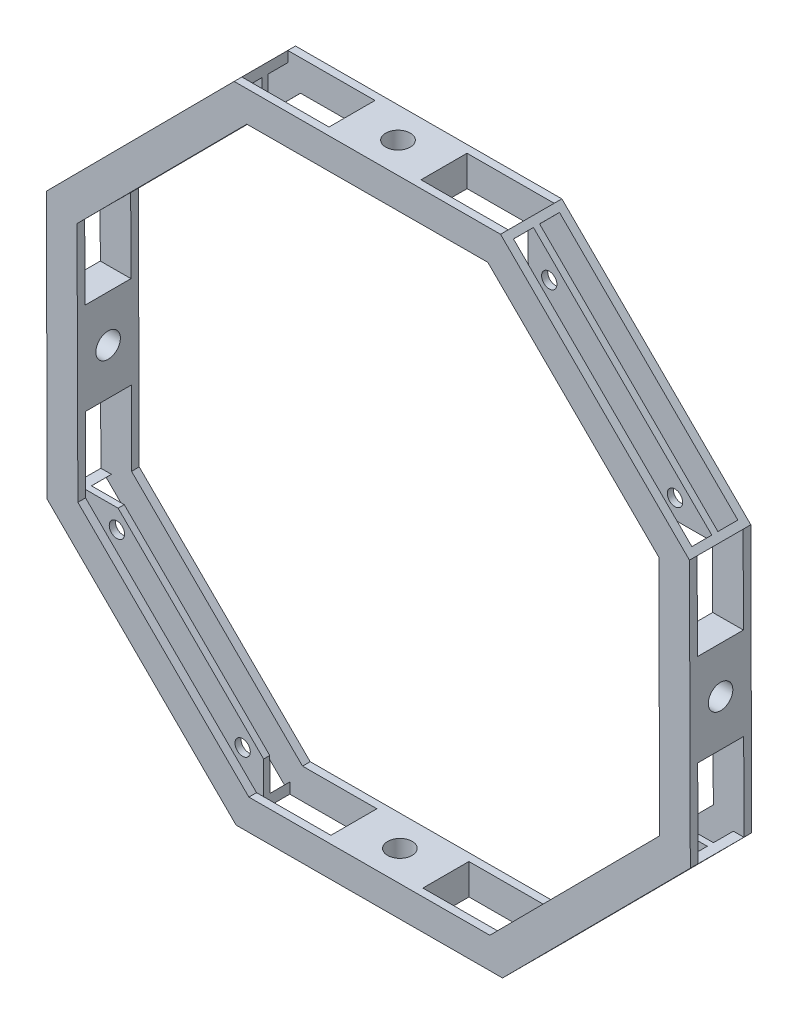
SolidWorks part; units mm, degrees
ref_plane "Plano frontal" through (0, 0, 0) normal (0, 0, 1) x (1, 0, 0)
ref_plane "Plano superior" through (0, 0, 0) normal (0, 1, 0) x (1, 0, 0)
ref_plane "Plano direito" through (0, 0, 0) normal (1, 0, 0) x (0, 0, -1)
sketch "Esboço1" plane through (0, 0, 0) normal (0, 0, 1) x (1, 0, 0)
  line L9 (209.462, 87.5228) -> (86.2241, 210)
  line L10 (86.2241, 210) -> (-87.5228, 209.462)
  line L11 (-87.5228, 209.462) -> (-210, 86.2241)
  line L12 (-210, 86.2241) -> (-209.462, -87.5228)
  line L13 (-209.462, -87.5228) -> (-86.2241, -210)
  line L14 (-86.2241, -210) -> (87.5228, -209.462)
  line L15 (87.5228, -209.462) -> (210, -86.2241)
  line L16 (210, -86.2241) -> (209.462, 87.5228)
  line L17 (189.4504, 79.2502) -> (77.9233, 190)
  line L18 (77.9233, 190) -> (-79.2502, 189.4504)
  line L19 (-79.2502, 189.4504) -> (-190, 77.9233)
  line L20 (-190, 77.9233) -> (-189.4504, -79.2502)
  line L21 (-189.4504, -79.2502) -> (-77.9233, -190)
  line L22 (-77.9233, -190) -> (79.2502, -189.4504)
  line L23 (79.2502, -189.4504) -> (190, -77.9233)
  line L24 (190, -77.9233) -> (189.4504, 79.2502)
  circle A0 centre (0, 0) radius 209.732 construction
  circle A1 centre (0, 0) radius 189.7264 construction
extrude "Ressalto-extrusão1" add sketch "Esboço1" along normal blind 40
sketch "Esboço2" plane through (209.731, 0.6494, 0) normal (1, 0.0031, 0) x (0, 0, -1)
  line L0 (-40, 86.8738) -> (0, 86.8738) construction
  line L1 (-40, -86.8738) -> (-40, 86.8738) construction
  line L3 (0, 0) -> (0, 29.9874)
  line L4 (0, 29.9874) -> (-40, 29.9874)
  line L5 (-40, 0) -> (-40, 29.9874)
  line L6 (0, 29.9874) -> (-5, 29.9874)
  line L8 (0, 0) -> (0, -30)
  line L9 (0, -30) -> (-40, -30)
  line L10 (-40, 0) -> (-40, -30)
  line L11 (0, 29.9874) -> (0, 86.8738)
  line L12 (0, 86.8738) -> (-5, 86.8738)
  line L13 (-5, 29.9874) -> (-5, 86.8738)
  line L14 (-40, -86.8738) -> (0, -86.8738) construction
  line L15 (-40, 29.9874) -> (-35, 29.9874)
  line L16 (-40, 29.9874) -> (-40, 86.8738)
  line L17 (-40, 86.8738) -> (-35, 86.8738)
  line L18 (-35, 29.9874) -> (-35, 86.8738)
  line L19 (-40, -30) -> (-35, -30)
  line L20 (-40, -30) -> (-40, -86.8738)
  line L21 (-40, -86.8738) -> (-35, -86.8738)
  line L22 (-35, -30) -> (-35, -86.8738)
  line L24 (0, -30) -> (-5, -30)
  line L25 (0, -30) -> (0, -86.8738)
  line L26 (0, -86.8738) -> (-5, -86.8738)
  line L27 (-5, -30) -> (-5, -86.8738)
  line M5 (0, 86.8738) -> (-40, 86.8738)
  line M7 (-40, -86.8738) -> (0, -86.8738)
extrude "Corte-extrusão2" cut sketch "Esboço2" against normal through all both and the other way through all contours L18 L4 L13 M5 region at (209.5501, 59.0797, 20)
sketch "Esboço4" plane through (209.731, 0.6494, 0) normal (1, 0.0031, 0) x (0, 0, -1)
  circle A0 centre (-20, 0) radius 8
extrude "Corte-extrusão3" cut sketch "Esboço4" against normal through all both and the other way through all
extrude "Corte-extrusão4" cut sketch "Esboço2<4>" against normal through all both and the other way through all contours L27 L9 L22 M7 region at (209.912, -57.7873, 20)
sketch "Esboço2<4>" plane through (209.731, 0.6494, 0) normal (1, 0.0031, 0) x (0, 0, -1) same geometry as "Esboço2"
sketch "Esboço15" plane through (-148.7614, 147.843, 0) normal (-0.7093, 0.7049, 0) x (0, 0, 1)
  line L0 (40, 86.8738) -> (0, 86.8738) construction
  line L1 (5, -86.8738) -> (35, -86.8738)
  line L2 (5, -86.8738) -> (5, 86.8738)
  line L3 (5, 86.8738) -> (35, 86.8738)
  line L4 (35, -86.8738) -> (35, 86.8738)
  line L6 (5, -86.8738) -> (35, -86.8738)
  line L7 (5, -86.8738) -> (5, -82)
  line L8 (5, -82) -> (35, -82)
  line L9 (35, -86.8738) -> (35, -82)
  line L10 (5, 86.8738) -> (35, 86.8738)
  line L11 (5, 86.8738) -> (5, 82)
  line L12 (5, 82) -> (35, 82)
  line L13 (35, 86.8738) -> (35, 82)
  line L14 (20, 82) -> (22, 82)
  line L15 (20, 82) -> (20, -82)
  line L16 (20, -82) -> (22, -82)
  line L17 (22, 82) -> (22, -82)
  line L18 (20, -82) -> (18, -82)
  line L19 (20, -82) -> (20, 82)
  line L20 (20, 82) -> (18, 82)
  line L21 (18, -82) -> (18, 82)
extrude "Corte-extrusão5" cut sketch "Esboço15" against normal through all both and the other way through all contours L12 L17 L8 L4 | L8 L21 L12 L2 region at (-148.7614, 147.843, 11.5) region at (-148.7614, 147.843, 28.5)
sketch "Esboço16" plane through (147.843, 148.7614, 0) normal (0.7049, 0.7093, 0) x (0, 0, -1)
  line L0 (-40, 86.8738) -> (0, 86.8738) construction
  line L1 (-35, -86.8738) -> (-5, -86.8738)
  line L2 (-35, -86.8738) -> (-35, 86.8738)
  line L3 (-35, 86.8738) -> (-5, 86.8738)
  line L4 (-5, -86.8738) -> (-5, 86.8738)
  line L6 (-35, -86.8738) -> (-5, -86.8738)
  line L7 (-35, -86.8738) -> (-35, -82)
  line L8 (-35, -82) -> (-5, -82)
  line L9 (-5, -86.8738) -> (-5, -82)
  line L10 (-5, 86.8738) -> (-35, 86.8738)
  line L11 (-5, 86.8738) -> (-5, 82)
  line L12 (-5, 82) -> (-35, 82)
  line L13 (-35, 86.8738) -> (-35, 82)
  line L14 (-20, 82) -> (-18, 82)
  line L16 (-20, -82) -> (-18, -82)
  line L17 (-18, 82) -> (-18, -82)
  line L18 (-20, -82) -> (-22, -82)
  line L20 (-20, 82) -> (-22, 82)
  line L21 (-22, -82) -> (-22, 82)
extrude "Corte-extrusão6" cut sketch "Esboço16" against normal through all both and the other way through all contours L8 L21 L12 L2 | L12 L17 L8 L4 region at (147.843, 148.7614, 28.5) region at (147.843, 148.7614, 11.5)
sketch "Esboço18" plane through (0.6494, -209.731, 0) normal (0.0031, -1, 0) x (1, 0.0031, 0)
  line L1 (-86.8738, 35) -> (86.8738, 35)
  line L2 (-86.8738, 35) -> (-86.8738, 5)
  line L3 (-86.8738, 5) -> (86.8738, 5)
  line L4 (86.8738, 35) -> (86.8738, 5)
ref_plane "Plano2" through (189.8304, -29.4124, 5) normal (1, 0.0031, 0) x (0, 0, -1)
sketch "Esboço21" plane through (-0.6494, 209.731, 0) normal (-0.0031, 1, 0) x (1, 0.0031, 0)
  line L0 (-86.8738, -5) -> (86.8738, -5) construction
  line L1 (0, -5) -> (30, -5)
  line L2 (0, -5) -> (0, -35)
  line L3 (0, -35) -> (30, -35)
  line L4 (30, -5) -> (30, -35)
  line L5 (-86.8738, -35) -> (86.8738, -35) construction
  line L7 (0, -5) -> (-30, -5)
  line L8 (0, -5) -> (0, -35)
  line L9 (0, -35) -> (-30, -35)
  line L10 (-30, -5) -> (-30, -35)
sketch "Esboço22" plane through (-0.6494, 209.731, 0) normal (-0.0031, 1, 0) x (1, 0.0031, 0)
  line L1 (-30, -5) -> (-86.8738, -5)
  line L2 (-30, -5) -> (-30, -35)
  line L3 (-30, -35) -> (-86.8738, -35)
  line L4 (-86.8738, -5) -> (-86.8738, -35)
  line L5 (30, -5) -> (86.8738, -5)
  line L6 (30, -5) -> (30, -35)
  line L7 (30, -35) -> (86.8738, -35)
  line L8 (86.8738, -5) -> (86.8738, -35)
extrude "Corte-extrusão8" cut sketch "Esboço22" against normal through all both and the other way through all
sketch "Esboço23" plane through (-0.6494, 209.731, 0) normal (-0.0031, 1, 0) x (1, 0.0031, 0)
  line L0 (0, -5) -> (0, -35) construction
  circle A0 centre (0, -20) radius 8
extrude "Corte-extrusão9" cut sketch "Esboço23" against normal through all both and the other way through all
sketch "Esboço26" plane through (0, 0, 18) normal (0, 0, -1) x (-1, 0, 0)
  circle A0 centre (100, 182) radius 5
  circle A1 centre (182, 100) radius 5
  circle A2 centre (-182, -100) radius 5
  circle A3 centre (-100, -182) radius 5
  circle A4 centre (100, -182) radius 5
  circle A5 centre (182, -100) radius 5
  circle A6 centre (-182, 100) radius 5
  circle A7 centre (-100, 182) radius 5
extrude "Corte-extrusão10" cut sketch "Esboço26" against normal blind 10
